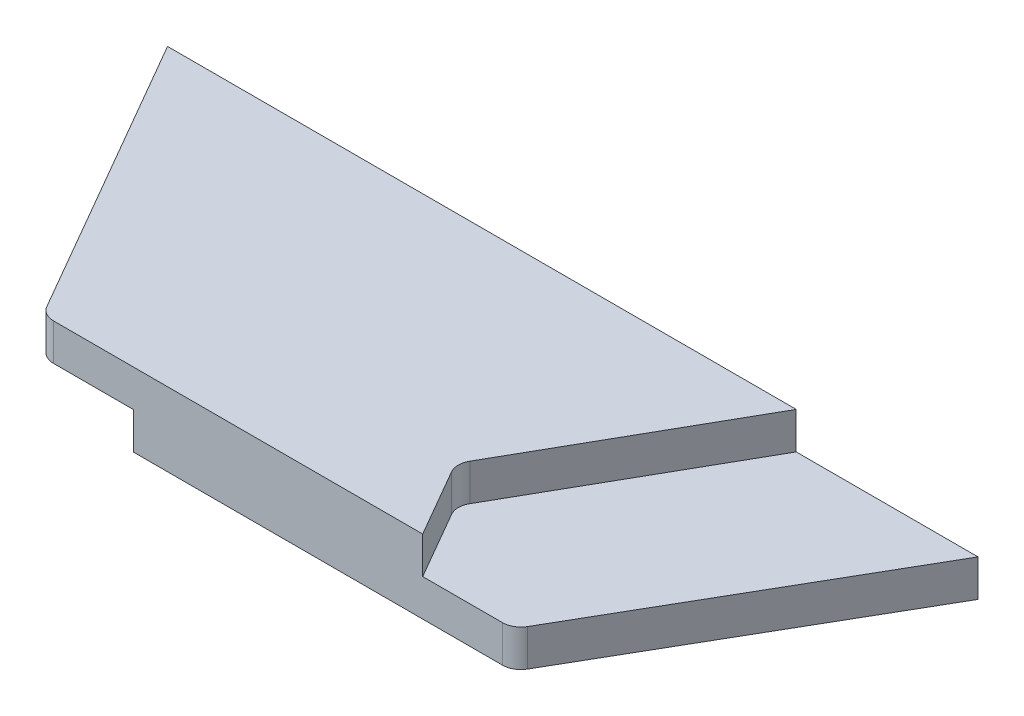
SolidWorks part; units mm, degrees
ref_plane "Спереди" through (0, 0, 0) normal (0, 0, 1) x (1, 0, 0)
ref_plane "Сверху" through (0, 0, 0) normal (0, 1, 0) x (1, 0, 0)
ref_plane "Справа" through (0, 0, 0) normal (1, 0, 0) x (0, 0, -1)
sketch "Эскиз1" plane through (0, 0, 0) normal (1, 0, 0) x (0, 0, -1)
  line L1 (0, 0) -> (80, 0)
  line L2 (0, 0) -> (0, 20)
  line L3 (0, 20) -> (80, 20)
  line L4 (80, 0) -> (80, 20)
extrude "Бобышка-Вытянуть1" add sketch "Эскиз1" along normal blind 220
sketch "Эскиз2" plane through (0, 0, 0) normal (0, -1, 0) x (1, 0, 0)
  line L1 (220, 0) -> (0, 0) construction
  line L2 (220, -80) -> (0, -80) construction
  line L3 (49.75, -80) -> (0, -80)
  line L4 (0, -80) -> (0, 0)
  line L5 (0, 0) -> (70.7402, 0)
  line L6 (81.9445, -24.4187) -> (49.75, -80)
  line L8 (70.7402, 0) -> (81.9481, -19.4126)
  arc A0 (81.9445, -24.4187) -> (81.9481, -19.4126) centre (77.6179, -21.9126) ccw
  point P11 (0, 0)
  point P12 (70.7402, 0)
  dimension "D1" = 5
extrude "Вырез-Вытянуть1" cut sketch "Эскиз2" against normal blind 10
sketch "Эскиз3" plane through (0, 20, 0) normal (0, 1, 0) x (1, 0, 0)
  line L1 (220, 0) -> (0, 0) construction
  line L2 (138.5312, 23.5275) -> (170.6576, 80)
  line L3 (220, 80) -> (0, 80) construction
  line L4 (170.6576, 80) -> (220, 80)
  line L5 (220, 80) -> (220, 0)
  line L6 (220, 0) -> (149.2598, 0)
  line L8 (138.547, 18.5551) -> (149.2598, 0)
  arc A0 (138.547, 18.5551) -> (138.5312, 23.5275) centre (142.8771, 21.0551) cw
  point P13 (149.2598, 0)
  dimension "D1" = 5
extrude "Вырез-Вытянуть2" cut sketch "Эскиз3" against normal blind 10
sketch "Эскиз4" plane through (0, 20, 0) normal (0, 1, 0) x (1, 0, 0)
  line L0 (220, 80) -> (175.2554, 2.5)
  line L1 (149.2598, 0) -> (220, 0) construction
  line L2 (170.9252, 0) -> (49.0748, 0)
  line L3 (149.2598, 0) -> (0, 0) construction
  line L4 (44.7446, 2.5) -> (0, 80)
  line L5 (0, 80) -> (0, 0) construction
  line L6 (170.6576, 80) -> (0, 80) construction
  line L7 (0, 80) -> (220, 80)
  arc A0 (175.2554, 2.5) -> (170.9252, 0) centre (170.9252, 5) cw
  arc A1 (49.0748, 0) -> (44.7446, 2.5) centre (49.0748, 5) cw
  point P15 (173.812, 0)
  point P18 (46.188, 0)
  dimension "D1" = 5
extrude "Вырез-Вытянуть4" cut sketch "Эскиз4" against normal through all flip side to cut
